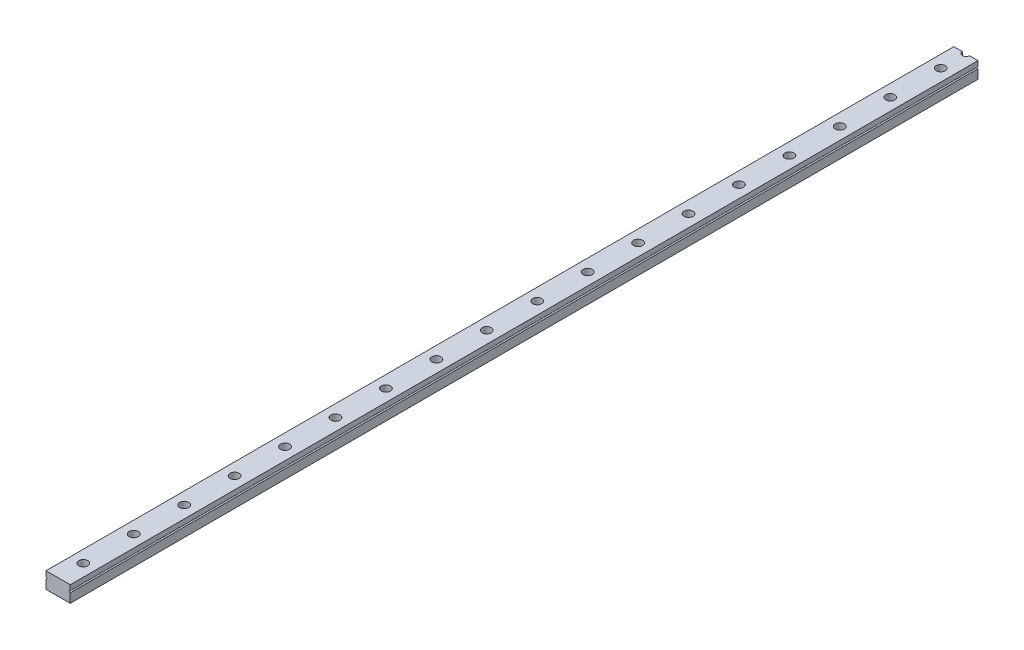
SolidWorks part; units mm, degrees
ref_plane "Front Plane" through (0, 0, 0) normal (0, 0, 1) x (1, 0, 0)
ref_plane "Top Plane" through (0, 0, 0) normal (0, 1, 0) x (1, 0, 0)
ref_plane "Right Plane" through (0, 0, 0) normal (1, 0, 0) x (0, 0, -1)
sketch "Rail-Sketch1" plane through (0, 0, 0) normal (0, 0, 1) x (1, 0, 0)
  line L0 (0, 0) -> (12, 0)
  line L1 (12, 0) -> (12, 4.5)
  line L2 (0, 4.5) -> (0, 0)
  line L3 (0, 8) -> (12, 8)
  line L4 (0, 8) -> (0, 5.5)
  line L5 (12, 8) -> (12, 5.5)
  arc A0 (0, 5.5) -> (0, 4.5) centre (0, 5) cw
  arc A1 (12, 5.5) -> (12, 4.5) centre (12, 5) ccw
  point P7 (0.5, 5)
  dimension "D2" = 8
  dimension "D5" = 11
  dimension "D3" = 2.5
extrude "Boss-Extrude1" add sketch "Rail-Sketch1" along normal blind 450
sketch "RailHoles-Sketch1" plane through (0, 8, 0) normal (0, 1, 0) x (1, 0, 0)
  line L0 (12, -450) -> (0, -450) construction
  line L1 (0, -450) -> (0, 0) construction
  line L2 (12, 0) -> (0, 0) construction
  line L3 (12, -450) -> (12, 0) construction
  circle A0 centre (6, -437.5) radius 1.75
  circle A25 centre (6, -412.5) radius 1.75
  circle A26 centre (6, -387.5) radius 1.75
  circle A27 centre (6, -362.5) radius 1.75
  circle A28 centre (6, -337.5) radius 1.75
  circle A29 centre (6, -312.5) radius 1.75
  circle A30 centre (6, -287.5) radius 1.75
  circle A31 centre (6, -262.5) radius 1.75
  circle A32 centre (6, -237.5) radius 1.75
  circle A33 centre (6, -212.5) radius 1.75
  circle A34 centre (6, -187.5) radius 1.75
  circle A35 centre (6, -162.5) radius 1.75
  circle A36 centre (6, -137.5) radius 1.75
  circle A37 centre (6, -112.5) radius 1.75
  circle A38 centre (6, -87.5) radius 1.75
  circle A39 centre (6, -62.5) radius 1.75
  circle A40 centre (6, -37.5) radius 1.75
  circle A41 centre (6, -12.5) radius 1.75
  circle A42 centre (6, 0) radius 1.75
  dimension "D3" = 3.5
  dimension "D1" = 12.5
  dimension "D2" = 6
  dimension "D5" = 6
  dimension "D4" = 18
extrude "RailHoles-Cut-Extrude1" cut sketch "RailHoles-Sketch1" against normal through all
sketch "RailBoreHolesSketch1" plane through (0, 8, 0) normal (0, 1, 0) x (1, 0, 0)
  circle A0 centre (6, -437.5) radius 2.25
  circle A1 centre (6, -412.5) radius 2.25
  circle A2 centre (6, -387.5) radius 2.25
  circle A3 centre (6, -362.5) radius 2.25
  circle A4 centre (6, -337.5) radius 2.25
  circle A5 centre (6, -312.5) radius 2.25
  circle A6 centre (6, -287.5) radius 2.25
  circle A7 centre (6, -262.5) radius 2.25
  circle A8 centre (6, -237.5) radius 2.25
  circle A9 centre (6, -212.5) radius 2.25
  circle A10 centre (6, -187.5) radius 2.25
  circle A11 centre (6, -162.5) radius 2.25
  circle A12 centre (6, -137.5) radius 2.25
  circle A13 centre (6, -112.5) radius 2.25
  circle A14 centre (6, -87.5) radius 2.25
  circle A15 centre (6, -62.5) radius 2.25
  circle A16 centre (6, -37.5) radius 2.25
  circle A17 centre (6, -12.5) radius 2.25
  dimension "D1" = 4.5
extrude "RailBoreHolesCut-Extrude1" cut sketch "RailBoreHolesSketch1" against normal blind 4
equation "\"LinearRailWidth\"= 12mm'Spec"
equation "\"D1@Rail-Sketch1\" = \"LinearRailWidth\""
equation "\"LinearRailHeight\"= 8mm'Spec"
equation "\"D2@Rail-Sketch1\" = \"LinearRailHeight\""
equation "\"LinearRailLength\"= 450mm'Spec"
equation "\"D1@Boss-Extrude1\"=\"LinearRailLength\""
equation "\"LinearRailHoleOuterBore\"= 4.5mm'Spec"
equation "\"LinearRailHoleDiameter\"= 3.5mm'Spec"
equation "\"LinearRailHoleOuterBoreDepth\"= 4mm'Spec"
equation "\"LinearRailHoleDistance\"= 25mm'Spec"
equation "\"LinearRailFirstHoleOffsetFromEdge\"= 12.5mm'Spec"
equation "\"D1@RailHoles-Sketch1\" = \"LinearRailFirstHoleOffsetFromEdge\""
equation "\"D2@RailHoles-Sketch1\" = \"LinearRailWidth\" / 2"
equation "\"D3@RailHoles-Sketch1\" = \"LinearRailHoleDiameter\""
equation "\"D1@RailBoreHolesSketch1\" = \"LinearRailHoleOuterBore\""
equation "\"D1@RailBoreHolesCut-Extrude1\"=\"LinearRailHoleOuterBoreDepth\""
